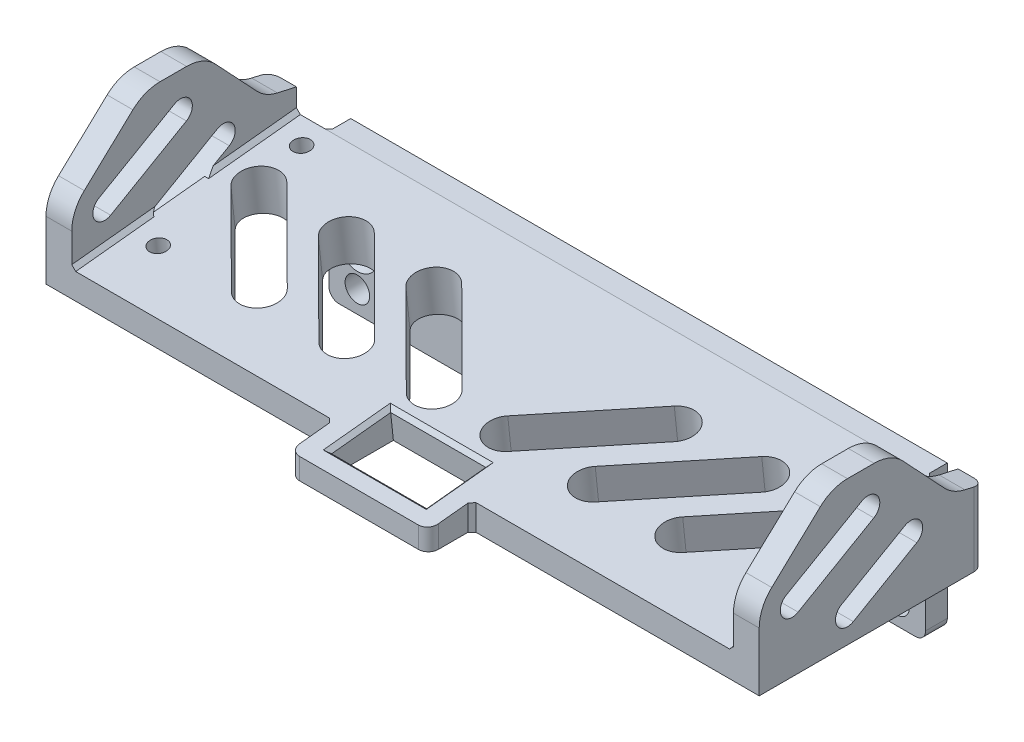
SolidWorks part; units mm, degrees
material "PPS"
ref_plane "前视基准面" through (0, 0, 0) normal (0, 0, 1) x (1, 0, 0)
ref_plane "上视基准面" through (0, 0, 0) normal (0, 1, 0) x (1, 0, 0)
ref_plane "右视基准面" through (0, 0, 0) normal (1, 0, 0) x (0, 0, -1)
sketch "ref" plane through (0, 0, 0) normal (0, 0, 1) x (1, 0, 0)
  line L257 (0, -1000) -> (0, 49000) construction
  line L346 (0, 0) -> (635.1265, 0) construction
  line L351 (-46.1708, 93.9243) -> (-46.1708, 145) construction
  line L358 (-27.9426, 92.9426) -> (-32.5, 97.5) construction
  line L394 (-24.4478, 142.8678) -> (-29.0158, 138.8343)
  line L411 (-32.3253, 137.5823) -> (-39.0335, 137.5823)
  line L414 (-42.3429, 136.3303) -> (-44.4803, 134.4431)
  line L445 (-46.1708, 130.695) -> (-46.1708, 101.1668)
  line L472 (42.3429, 136.3303) -> (44.4803, 134.4431)
  line L494 (46.1729, 155.4291) -> (33.7932, 145.5483) construction
  line L496 (32.4724, 137.5823) -> (39.0335, 137.5823)
  line L497 (25.2455, 142.6568) -> (28.9763, 139.0078)
  line L498 (27.9426, 92.9426) -> (32.5, 97.5) construction
  line L501 (-46.2756, 154.6927) -> (-33.8959, 144.8119) construction
  line L595 (-39.3354, 129.0823) -> (-39.3354, 104.0823) construction
  line L626 (-31.6538, 83.28) -> (-46.1708, 93.9243) construction
  line L628 (-39.3354, 116.5823) -> (0, 116.5823) construction
  line L629 (-15.0322, 144.0823) -> (-9.5322, 138.5823)
  line L630 (-9.5322, 138.5823) -> (9.5322, 138.5823)
  line L631 (15.0322, 144.0823) -> (9.5322, 138.5823)
  line L633 (-21.7494, 144.0823) -> (-15.0322, 144.0823)
  line L635 (15.0322, 144.0823) -> (21.7494, 144.0823)
  line L641 (-9.5322, 83.7633) -> (9.5322, 83.7633)
  line L643 (-9.5322, 83.7633) -> (-14.5322, 78.7633)
  line L644 (30.4418, 78.7633) -> (14.5322, 78.7633) construction
  line L645 (9.5322, 83.7633) -> (14.5322, 78.7633)
  line L646 (7.1054, 96.1323) -> (-7.1054, 96.1323)
  line L647 (-7.1054, 96.1323) -> (-9.7615, 92.339)
  line L648 (-9.7615, 92.339) -> (-9.7615, 90.339)
  line L649 (-9.7615, 90.339) -> (9.7615, 90.339)
  line L652 (9.7615, 92.339) -> (9.7615, 90.339)
  line L653 (7.1054, 96.1323) -> (9.7615, 92.339)
  line L666 (-35.6, 116.5823) -> (-35.6, 112.0823)
  line L668 (-32.5, 116.5823) -> (-32.5, 112.0823)
  line L670 (35.6, 116.5823) -> (35.6, 112.0823)
  line L671 (32.5, 116.5823) -> (32.5, 112.0823)
  line L681 (-19.6882, 78.7633) -> (-14.5322, 78.7633)
  line L686 (14.5322, 78.7633) -> (19.6882, 78.7633)
  line L687 (-42.4964, 96.1323) -> (-35.6, 93.9243)
  line L688 (-35.6, 93.9243) -> (-30.0524, 90.888)
  line L691 (-30.0524, 90.888) -> (-30.0524, 87.8422)
  line L692 (-30.0524, 87.8422) -> (-19.6882, 78.7633)
  line L693 (30.0524, 87.8422) -> (19.6882, 78.7633)
  line L694 (30.0524, 90.888) -> (30.0524, 87.8422)
  line L695 (35.6, 93.9243) -> (30.0524, 90.888)
  line L696 (42.4964, 96.1323) -> (35.6, 93.9243)
  line L697 (46.1708, 130.695) -> (46.1708, 101.1668)
  line L700 (-17.1276, 113.853) -> (-11.5061, 107.6186)
  line L701 (-11.5061, 107.6186) -> (11.5061, 107.6186)
  line L706 (17.1276, 113.853) -> (11.5061, 107.6186)
  line L709 (-7.1054, 129.7982) -> (7.1054, 129.7982)
  line L710 (7.1054, 129.7982) -> (9.7615, 133.5915)
  line L711 (9.7615, 133.5915) -> (9.7615, 135.5915)
  line L712 (9.7615, 135.5915) -> (-9.7615, 135.5915)
  line L713 (-9.7615, 133.5915) -> (-9.7615, 135.5915)
  line L714 (-7.1054, 129.7982) -> (-9.7615, 133.5915)
  line L715 (-24.5927, 117.0678) -> (26.26, 117.0678) construction
  line L717 (17.1276, 113.853) -> (17.1276, 120.2826)
  line L719 (-17.1276, 113.853) -> (-17.1276, 120.2826)
  line L720 (17.1276, 120.2826) -> (11.5061, 126.517)
  line L721 (-17.1276, 120.2826) -> (-11.5061, 126.517)
  line L722 (-11.5061, 126.517) -> (11.5061, 126.517)
  line L723 (-24.5927, 127.9437) -> (-24.5927, 106.192) construction
  line L724 (-22.2052, 127.9437) -> (-22.2052, 106.192)
  line L725 (-26.9801, 127.9437) -> (-26.9801, 106.192)
  line L726 (24.5927, 127.9437) -> (24.5927, 106.192) construction
  line L727 (22.2052, 127.9437) -> (22.2052, 106.192)
  line L728 (26.9801, 127.9437) -> (26.9801, 106.192)
  circle A384 centre (39.3354, 129.0823) radius 2.75
  circle A385 centre (39.3354, 104.0823) radius 2.75
  circle A390 centre (17.238, 84.7633) radius 2.75
  circle A420 centre (-17.238, 84.7633) radius 2.75
  circle A421 centre (-39.3354, 104.0823) radius 2.75
  circle A422 centre (-39.3354, 129.0823) radius 2.75
  arc A453 (32.7926, 143.0294) -> (32.5, 97.5) centre (-120.6696, 121.25) cw construction
  arc A454 (-32.8936, 142.3057) -> (-32.5, 97.5) centre (120.6696, 121.25) ccw construction
  arc A455 (-27.9426, 92.9426) -> (27.9426, 92.9426) centre (0, 290.981) ccw construction
  arc A456 (33.7932, 145.5483) -> (32.7926, 143.0294) centre (35.4973, 143.4132) ccw construction
  arc A457 (-32.8936, 142.3057) -> (-33.8959, 144.8119) centre (-35.6, 142.6768) ccw construction
  arc A473 (-44.4803, 134.4431) -> (-46.1708, 130.695) centre (-41.1708, 130.695) ccw
  arc A474 (-39.0335, 137.5823) -> (-42.3429, 136.3303) centre (-39.0335, 132.5823) ccw
  arc A475 (46.1708, 130.695) -> (44.4803, 134.4431) centre (41.1708, 130.695) ccw
  arc A476 (42.3429, 136.3303) -> (39.0335, 137.5823) centre (39.0335, 132.5823) ccw
  arc A477 (32.4724, 137.5823) -> (28.9763, 139.0078) centre (32.4724, 142.5823) cw
  arc A478 (-29.0158, 138.8343) -> (-32.3253, 137.5823) centre (-32.3253, 142.5823) cw
  arc A479 (25.2455, 142.6568) -> (21.7494, 144.0823) centre (21.7494, 139.0823) ccw
  arc A480 (-21.7494, 144.0823) -> (-24.4478, 142.8678) centre (-21.1384, 139.1198) ccw
  arc A481 (-35.6, 116.5823) -> (-32.5, 116.5823) centre (-34.05, 116.5823) cw
  arc A484 (-35.6, 112.0823) -> (-32.5, 112.0823) centre (-34.05, 112.0823) ccw
  arc A486 (35.6, 116.5823) -> (32.5, 116.5823) centre (34.05, 116.5823) ccw
  arc A487 (35.6, 112.0823) -> (32.5, 112.0823) centre (34.05, 112.0823) cw
  arc A490 (-46.1708, 101.1668) -> (-42.4964, 96.1323) centre (-40.8846, 101.1668) ccw
  arc A491 (46.1708, 101.1668) -> (42.4964, 96.1323) centre (40.8846, 101.1668) cw
  circle A492 centre (17.25, 134.3178) radius 2.75
  circle A493 centre (17.25, 99.8178) radius 2.75
  circle A494 centre (-17.25, 99.8178) radius 2.75
  circle A495 centre (-17.25, 134.3178) radius 2.75
  arc A496 (-22.2052, 127.9437) -> (-26.9801, 127.9437) centre (-24.5927, 127.9437) ccw
  arc A497 (-26.9801, 106.192) -> (-22.2052, 106.192) centre (-24.5927, 106.192) ccw
  arc A498 (22.2052, 127.9437) -> (26.9801, 127.9437) centre (24.5927, 127.9437) cw
  arc A499 (26.9801, 106.192) -> (22.2052, 106.192) centre (24.5927, 106.192) cw
  point P15 (0, 78.5133)
  point P20 (-24.5927, 117.0678)
  point P46 (-46.1708, 132.9503)
  point P50 (-40.925, 137.5823)
  point P53 (46.1708, 132.9503)
  point P56 (40.925, 137.5823)
  point P59 (30.4337, 137.5823)
  point P62 (-30.4337, 137.5823)
  point P65 (23.8205, 144.5823)
  point P69 (-23.8205, 144.5823)
  point P76 (0, 138.5823)
  point P90 (0, 90.339)
  point P92 (0, 96.1323)
  point P118 (0.085, 119.8323)
  point P121 (0, 107.6186)
  point P123 (24.5927, 117.0678)
  point P133 (0, 135.5915)
  point P136 (0, 129.7982)
  point P144 (17.1276, 117.0678)
  point P151 (-17.1276, 117.0678)
  dimension "D1" = 84.7633
  dimension "D2" = 17.238
  dimension "D5" = 44.319
  dimension "D6" = 19.319
  dimension "D7" = 22.0974
  dimension "D8" = 22.0974
  dimension "D9" = 6.5
  dimension "D11" = 46.1708
  dimension "D15" = 33.5
  dimension "D17" = 6
  dimension "D38" = 5.5
  dimension "D39" = 155
  dimension "D40" = 200
  dimension "D27" = 135
  dimension "D31" = 1.55
  dimension "D18" = 34.5
  dimension "D10" = 138.556
  dimension "D12" = 31.6538
  dimension "D13" = 93.9243
  dimension "D14" = 83.28
  dimension "D16" = 5.5
  dimension "D19" = 34.5
  dimension "D25" = 5
  dimension "D26" = 135
  dimension "D28" = 125
  dimension "D29" = 2
  dimension "D30" = 20.45
  dimension "D32" = 32.5
  dimension "D33" = 4.5
sketch "底座" plane through (0, 0, 0) normal (0, 0, 1) x (1, 0, 0)
  line L0 (-37.6416, 127.5678) -> (37.6416, 127.5678)
  line L3 (0, 0) -> (0, 218.6335) construction
  line L4 (0, -201000) -> (0, 249000) construction
  line L5 (-37.6416, 127.5678) -> (-37.6416, 109.336)
  line L8 (-37.6416, 109.336) -> (-17.4308, 109.336)
  line L9 (-17.4308, 109.336) -> (-12.5008, 103.8686)
  line L10 (-12.5008, 103.8686) -> (12.5008, 103.8686)
  line L11 (17.4308, 109.336) -> (12.5008, 103.8686)
  line L12 (37.6416, 109.336) -> (17.4308, 109.336)
  line L13 (37.6416, 127.5678) -> (37.6416, 109.336)
  line L14 (-17.1276, 117.0678) -> (17.1276, 117.0678)
  line L15 (-17.1276, 113.853) -> (-17.1276, 120.2826) construction
  line L16 (17.1276, 117.0678) -> (17.1276, 113.853)
  line L17 (17.1276, 113.853) -> (11.5061, 107.6186)
  line L18 (11.5061, 107.6186) -> (-11.5061, 107.6186)
  line L19 (-11.5061, 107.6186) -> (-17.1276, 113.853)
  line L20 (-17.1276, 113.853) -> (-17.1276, 117.0678)
  circle A5 centre (-34.05, 116.5823) radius 1.55
  circle A6 centre (-34.05, 112.0823) radius 1.55
  circle A7 centre (34.05, 116.5823) radius 1.55
  circle A8 centre (34.05, 112.0823) radius 1.55
  point P22 (0, 103.8686)
  point P33 (0, 127.5678)
  dimension "D1" = 10.5
  dimension "D2" = 3.75
  dimension "D3" = 3.25
extrude "相机底座" add sketch "底座" along normal blind 2.75
sketch "相机支座" plane through (0, 0, 0) normal (1, 0, 0) x (0, 0, -1)
  line L4 (-2.75, 127.5678) -> (-57.8263, 127.5678) construction
  line L6 (-2.75, 127.5678) -> (-31.0939, 124.5888)
  line L7 (-31.0939, 124.5888) -> (-31.0939, 121.3388)
  line L8 (-31.0939, 121.3388) -> (-2.75, 121.3388)
  line L9 (-2.75, 127.5678) -> (-2.75, 109.336) construction
  line L10 (-2.75, 121.3388) -> (-2.75, 127.5678)
  dimension "D1" = 6
  dimension "D2" = 3.25
  dimension "D3" = 28.5
extrude "相机安装座" add sketch "相机支座" along normal blind 45 and the other way blind 45
sketch "USB线槽凸起" plane through (0, 121.3388, 113.8269) normal (0, 1, 0) x (-1, 0, 0)
  line L6 (0, -82.733) -> (0, -111.0769) construction
  line L7 (45, -82.733) -> (-45, -82.733) construction
  line L8 (-37.6416, -111.0769) -> (37.6416, -111.0769) construction
  line L9 (-8.75, -82.733) -> (-8.75, -77.233)
  line L10 (-8.75, -77.233) -> (8.75, -77.233)
  line L11 (8.75, -77.233) -> (8.75, -82.733)
  line L12 (8.75, -82.733) -> (-8.75, -82.733)
  dimension "D2" = 5.5
  dimension "D3" = 17.5
extrude "USB凸起" add sketch "USB线槽凸起" along normal up to surface (3.25 mm away) up to face at (0, 126.5748, 12.198)
sketch "相机减重和螺丝位" plane through (0, 126.4599, 13.2915) normal (0, 0.9945, 0.1045) x (1, 0, 0)
  line L0 (0, -17.9005) -> (0, 10.5995) construction
  line L5 (37.6416, 10.5995) -> (-37.6416, 10.5995) construction
  line L6 (-8.75, -17.9005) -> (8.75, -17.9005) construction
  line L7 (-6, -13.4308) -> (6, -13.4308)
  line L8 (6, -13.4308) -> (6, -20.9308)
  line L9 (6, -20.9308) -> (-6, -20.9308)
  line L10 (-6, -20.9308) -> (-6, -13.4308)
  line L12 (-8.75, -23.4308) -> (8.75, -23.4308) construction
  line L13 (26.2141, 1.318) -> (15.6789, -9.2172) construction
  line L14 (27.9819, -0.4497) -> (17.4467, -10.9849)
  line L15 (24.4463, 3.0858) -> (13.9111, -7.4494)
  line L16 (15.178, 1.318) -> (4.6428, -9.2172) construction
  line L17 (16.9457, -0.4497) -> (6.4105, -10.9849)
  line L18 (13.4102, 3.0858) -> (2.875, -7.4494)
  line L19 (26.2141, 1.318) -> (15.178, 1.318) construction
  line L20 (37.2503, 1.318) -> (26.715, -9.2172) construction
  line L21 (39.018, -0.4497) -> (28.4828, -10.9849)
  line L22 (35.4825, 3.0858) -> (24.9473, -7.4494)
  line L23 (37.2503, 1.318) -> (26.2141, 1.318) construction
  line L24 (-37.2503, 1.318) -> (-26.715, -9.2172) construction
  line L25 (-39.018, -0.4497) -> (-28.4828, -10.9849)
  line L26 (-35.4825, 3.0858) -> (-24.9473, -7.4494)
  line L27 (-26.2141, 1.318) -> (-15.6789, -9.2172) construction
  line L28 (-27.9819, -0.4497) -> (-17.4467, -10.9849)
  line L29 (-24.4463, 3.0858) -> (-13.9111, -7.4494)
  line L30 (-15.178, 1.318) -> (-4.6428, -9.2172) construction
  line L31 (-16.9457, -0.4497) -> (-6.4105, -10.9849)
  line L32 (-13.4102, 3.0858) -> (-2.875, -7.4494)
  circle A0 centre (38.1, -10.6005) radius 1.1
  circle A1 centre (-38.1, -10.6005) radius 1.1
  circle A2 centre (38.1, 7.5995) radius 1.1
  circle A3 centre (-38.1, 7.5995) radius 1.1
  arc A4 (27.9819, -0.4497) -> (24.4463, 3.0858) centre (26.2141, 1.318) ccw
  arc A5 (13.9111, -7.4494) -> (17.4467, -10.9849) centre (15.6789, -9.2172) ccw
  arc A6 (16.9457, -0.4497) -> (13.4102, 3.0858) centre (15.178, 1.318) ccw
  arc A7 (2.875, -7.4494) -> (6.4105, -10.9849) centre (4.6428, -9.2172) ccw
  arc A8 (39.018, -0.4497) -> (35.4825, 3.0858) centre (37.2503, 1.318) ccw
  arc A9 (24.9473, -7.4494) -> (28.4828, -10.9849) centre (26.715, -9.2172) ccw
  arc A10 (-39.018, -0.4497) -> (-35.4825, 3.0858) centre (-37.2503, 1.318) cw
  arc A11 (-24.9473, -7.4494) -> (-28.4828, -10.9849) centre (-26.715, -9.2172) cw
  arc A12 (-27.9819, -0.4497) -> (-24.4463, 3.0858) centre (-26.2141, 1.318) cw
  arc A13 (-13.9111, -7.4494) -> (-17.4467, -10.9849) centre (-15.6789, -9.2172) cw
  arc A14 (-16.9457, -0.4497) -> (-13.4102, 3.0858) centre (-15.178, 1.318) cw
  arc A15 (-2.875, -7.4494) -> (-6.4105, -10.9849) centre (-4.6428, -9.2172) cw
  point P24 (20.9465, -3.9496)
  point P29 (9.9104, -3.9496)
  point P41 (31.9826, -3.9496)
  point P51 (-31.9826, -3.9496)
  point P58 (-20.9465, -3.9496)
  point P65 (-9.9104, -3.9496)
  dimension "D4" = 2.2
  dimension "D1" = 18.2
  dimension "D2" = 3
  dimension "D3" = 76.2
  dimension "D5" = 7.5
  dimension "D6" = 2.5
  dimension "D7" = 12
  dimension "D8" = 45
  dimension "D9" = 5
extrude "相机面细节" cut sketch "相机减重和螺丝位" against normal up to surface (2.9494 mm away) up to face at (0, 121.3388, 20.8563)
sketch "结构支撑" plane through (0, 0, 0) normal (1, 0, 0) x (0, 0, -1)
  line L0 (-6.4122, 121.3388) -> (-2.75, 121.3388)
  line L1 (-31.0939, 121.3388) -> (-2.75, 121.3388) construction
  line L2 (-2.75, 121.3388) -> (-2.75, 119.5442)
  line L3 (-2.75, 109.336) -> (-2.75, 121.3388) construction
  line L4 (-2.75, 119.5442) -> (-6.4122, 121.3388)
extrude "相机面结构补强-1" add sketch "结构支撑" along normal blind 5 from offset 15
extrude "相机面结构补强-2" add sketch "结构支撑<2>" against normal blind 5 from offset 15 offset against normal yes
sketch "结构支撑<2>" plane through (0, 0, 0) normal (1, 0, 0) x (0, 0, -1) same geometry as "结构支撑"
sketch "相机保护" plane through (45, 0, 0) normal (1, 0, 0) x (0, 0, -1)
  line L0 (-31.0939, 121.3388) -> (-31.0939, 130.9161)
  line L1 (-31.0939, 130.9161) -> (-21.9356, 139.5107)
  line L2 (-21.9356, 139.5107) -> (-14.4356, 139.5107)
  line L3 (-14.4356, 139.5107) -> (-6.6494, 131.2139)
  line L5 (-2.75, 121.3388) -> (-31.0939, 121.3388)
  line L6 (-6.6494, 131.2139) -> (-2.75, 130.3511)
  line L7 (-2.75, 130.3511) -> (-2.75, 121.3388)
  line L8 (-17.3769, 134.8585) -> (-26.9355, 129.3399) construction
  line L9 (-16.6269, 133.5594) -> (-26.1855, 128.0408)
  line L10 (-18.1269, 136.1575) -> (-27.6855, 130.6389)
  line L11 (-17.3769, 134.8585) -> (-11.9635, 129.445) construction
  line L15 (-11.9635, 129.445) -> (-19.9671, 124.8241) construction
  line L16 (-11.2135, 128.146) -> (-19.2171, 123.5251)
  line L17 (-12.7135, 130.7441) -> (-20.7171, 126.1232)
  arc A0 (-16.6269, 133.5594) -> (-18.1269, 136.1575) centre (-17.3769, 134.8585) ccw
  arc A1 (-27.6855, 130.6389) -> (-26.1855, 128.0408) centre (-26.9355, 129.3399) ccw
  arc A4 (-11.2135, 128.146) -> (-12.7135, 130.7441) centre (-11.9635, 129.445) ccw
  arc A5 (-20.7171, 126.1232) -> (-19.2171, 123.5251) centre (-19.9671, 124.8241) ccw
  point P3 (-22.1562, 132.0992)
  point P27 (-15.9653, 127.1346)
  line M8 (-2.75, 127.5678) -> (-31.0939, 124.5888)
  dimension "D4" = 1.5
  dimension "D1" = 15.5
  dimension "D2" = 7.5
  dimension "D3" = 60
  dimension "D5" = 45
extrude "相机保护-右" add sketch "相机保护" against normal blind 3.25
extrude "相机保护-左" add sketch "相机保护<2>" along normal blind 3.25 from surface starting at face at (-45, 123.7085, 16.9219)
sketch "相机保护<2>" plane through (45, 0, 0) normal (1, 0, 0) x (0, 0, -1) same geometry as "相机保护"
extrude "美观-1" cut sketch "相机保护<3>" against normal blind 3.25 from surface contours L17 A5 L16 A4 M8 | A5 L16 M8 region at (45, 124.9499, 18.8029) region at (45, 128.0735, 14.7457) starting at face at (45, 127.5543, 15.7864)
sketch "相机保护<3>" plane through (45, 0, 0) normal (1, 0, 0) x (0, 0, -1) same geometry as "相机保护"
extrude "美观-2" cut sketch "相机保护<4>" along normal blind 3.25 from surface contours A5 L16 M8 | L17 A5 L16 A4 M8 region at (45, 124.9499, 18.8029) region at (45, 128.0735, 14.7457) starting at face at (-45, 127.5543, 15.7864)
sketch "相机保护<4>" plane through (45, 0, 0) normal (1, 0, 0) x (0, 0, -1) same geometry as "相机保护"
chamfer "倒角1" distance 0.5 angle 45 18 edges at (17.1276, 115.4604, 2.75) (14.3168, 110.7358, 2.75) (0, 107.6186, 2.75) (-14.3168, 110.7358, 2.75) (-17.1276, 115.4604, 2.75) (0, 117.0678, 2.75) (0, 125.056, 26.6487) (6, 124.664, 30.3781) (0, 124.272, 34.1076) (-6, 124.664, 30.3781) (8.75, 122.9638, 31.0939) (-8.75, 122.9638, 31.0939) (-41.75, 126.9597, 8.5357) (-41.75, 125.1068, 26.1647) (41.75, 126.9597, 8.5357) (41.75, 125.1068, 26.1647) (37.6416, 124.4533, 2.75) (-37.6416, 124.4533, 2.75)
chamfer "倒角2" distance 1 angle 45 2 edges at (35.6, 116.5823, 2.75) (-32.5, 116.5823, 2.75)
fillet "圆角1" radius 1.25 6 edges at (-8.75, 122.6747, 36.5939) (8.75, 122.6747, 36.5939) (-45, 125.8449, 2.75) (45, 125.8449, 2.75) (-37.6416, 109.336, 1.375) (37.6416, 109.336, 1.375)
fillet "圆角2" radius 5 12 edges at (-17.4308, 109.336, 1.375) (-12.5008, 103.8686, 1.375) (12.5008, 103.8686, 1.375) (17.4308, 109.336, 1.375) (-43.375, 131.2139, 6.6494) (-43.375, 139.5107, 14.4356) (-43.375, 139.5107, 21.9356) (43.375, 131.2139, 6.6494) (43.375, 139.5107, 14.4356) (43.375, 139.5107, 21.9356) (43.375, 130.9161, 31.0939) (-43.375, 130.9161, 31.0939)
sketch "螺母位" plane through (0, 127.8211, 0.3397) normal (0, -0.9945, -0.1045) x (1, 0, 0)
  line L25 (36.6566, 21.1235) -> (39.5434, 21.1235)
  line L26 (39.5434, 21.1235) -> (40.9868, 23.6235)
  line L27 (40.9868, 23.6235) -> (39.5434, 26.1235)
  line L28 (39.5434, 26.1235) -> (36.6566, 26.1235)
  line L29 (36.6566, 26.1235) -> (35.2132, 23.6235)
  line L30 (35.2132, 23.6235) -> (36.6566, 21.1235)
  line L31 (36.6566, 2.9235) -> (39.5434, 2.9235)
  line L32 (39.5434, 2.9235) -> (40.9868, 5.4235)
  line L33 (40.9868, 5.4235) -> (39.5434, 7.9235)
  line L34 (39.5434, 7.9235) -> (36.6566, 7.9235)
  line L35 (36.6566, 7.9235) -> (35.2132, 5.4235)
  line L36 (35.2132, 5.4235) -> (36.6566, 2.9235)
  line L37 (-40.9868, 23.6235) -> (-39.5434, 21.1235)
  line L38 (-39.5434, 21.1235) -> (-36.6566, 21.1235)
  line L39 (-36.6566, 21.1235) -> (-35.2132, 23.6235)
  line L40 (-35.2132, 23.6235) -> (-36.6566, 26.1235)
  line L41 (-36.6566, 26.1235) -> (-39.5434, 26.1235)
  line L42 (-39.5434, 26.1235) -> (-40.9868, 23.6235)
  line L43 (-39.5434, 2.9235) -> (-36.6566, 2.9235)
  line L44 (-36.6566, 2.9235) -> (-35.2132, 5.4235)
  line L45 (-35.2132, 5.4235) -> (-36.6566, 7.9235)
  line L46 (-36.6566, 7.9235) -> (-39.5434, 7.9235)
  line L47 (-39.5434, 7.9235) -> (-40.9868, 5.4235)
  line L48 (-40.9868, 5.4235) -> (-39.5434, 2.9235)
  circle A0 centre (38.1, 23.6235) radius 2.5 construction
  circle A1 centre (38.1, 23.6235) radius 1.1 construction
  circle A2 centre (38.1, 5.4235) radius 2.5 construction
  circle A3 centre (38.1, 5.4235) radius 1.1 construction
  circle A4 centre (-38.1, 5.4235) radius 1.1 construction
  circle A5 centre (-38.1, 23.6235) radius 2.5 construction
  circle A6 centre (-38.1, 5.4235) radius 2.5 construction
  circle A7 centre (-38.1, 23.6235) radius 1.1 construction
  dimension "D1" = 5
extrude "切除-拉伸6" cut sketch "螺母位" against normal blind 1.25 and the other way blind 4 from offset 4.5
